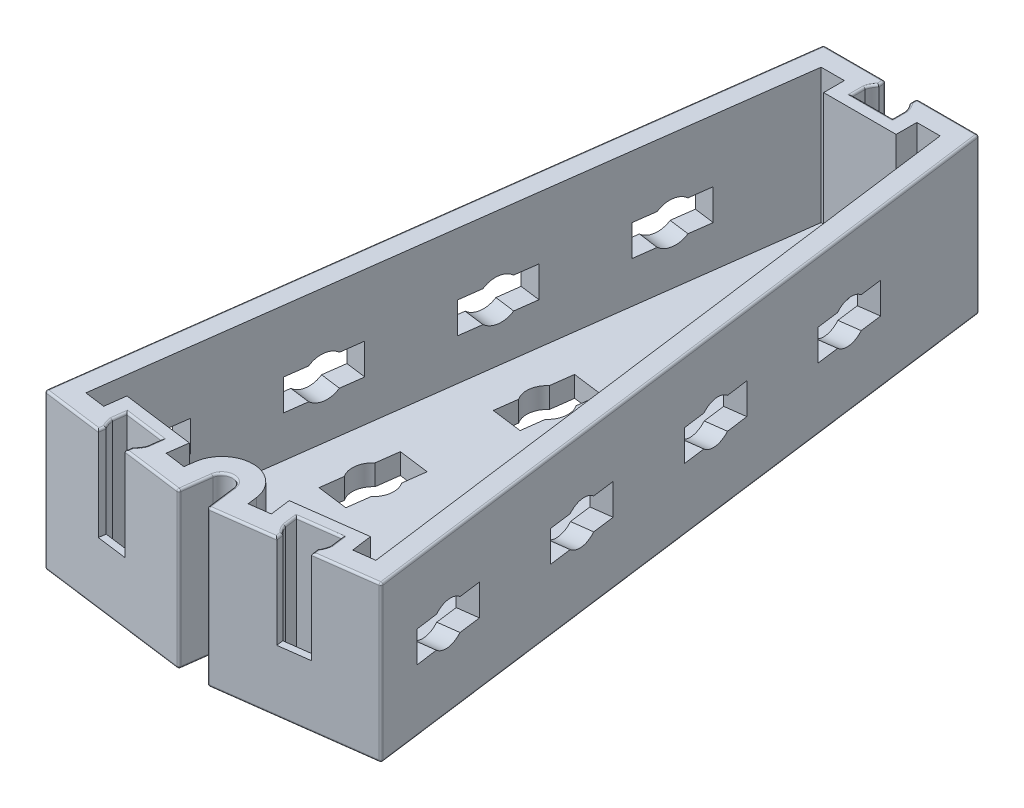
SolidWorks part; units mm, degrees
ref_plane "前视基准面" through (0, 0, 0) normal (0, 0, 1) x (1, 0, 0)
ref_plane "上视基准面" through (0, 0, 0) normal (0, 1, 0) x (1, 0, 0)
ref_plane "右视基准面" through (0, 0, 0) normal (1, 0, 0) x (0, 0, -1)
sketch "草图1" plane through (0, 0, 0) normal (0, 1, 0) x (1, 0, 0)
  line L0 (0, 0) -> (-7.5, 0)
  line L1 (0, 0) -> (7.5, 0)
  line L2 (-7.5, 0) -> (-16.25, -66.4628)
  line L3 (7.5, 0) -> (16.25, -66.4628)
  line L4 (-16.25, -66.4628) -> (-1.3783, -68.4207)
  line L5 (16.25, -66.4628) -> (1.3783, -68.4207)
  line L6 (-1.3783, -68.4207) -> (-0.9914, -65.4821)
  line L7 (1.3783, -68.4207) -> (0.9914, -65.4821)
  arc A0 (0.9914, -65.4821) -> (-0.9914, -65.4821) centre (0, -65.6126) ccw
  dimension "D11" = 2
  dimension "D1" = 7.5
  dimension "D2" = 7.5
  dimension "D3" = 97.5
  dimension "D4" = 97.5
  dimension "D5" = 32.5
  dimension "D6" = 15
  dimension "D7" = 67.0364
  dimension "D8" = 90
  dimension "D9" = 15
  dimension "D10" = 90
extrude "凸台-拉伸1" add sketch "草图1" along normal blind 15
sketch "草图2" plane through (0, 15, 0) normal (0, 1, 0) x (1, 0, 0)
  line L7 (-3.5, -2) -> (-3.5, -4)
  line L8 (-3.5, -4) -> (3.5, -4)
  line L9 (3.5, -4) -> (3.5, -2)
  line L10 (-3.5, -2) -> (-5.746, -2)
  line L11 (-12.0232, -65.0021) -> (-11.7621, -63.0192)
  line L12 (-11.7621, -63.0192) -> (-4.822, -63.9329)
  line L13 (-4.822, -63.9329) -> (-5.0831, -65.9157)
  line L14 (5.746, -2) -> (-5.746, -2)
  line L15 (-5.746, -2) -> (-14.0061, -64.741)
  line L16 (-14.0061, -64.741) -> (-3.1002, -66.1768)
  line L17 (-3.1002, -66.1768) -> (-2.9743, -65.221)
  line L18 (2.9743, -65.221) -> (3.1002, -66.1768)
  line L19 (3.1002, -66.1768) -> (14.0061, -64.741)
  line L20 (14.0061, -64.741) -> (5.746, -2)
  line L21 (5.746, -2) -> (3.5, -2)
  line L22 (-5.746, -2) -> (-14.0061, -64.741)
  line L23 (-14.0061, -64.741) -> (-12.0232, -65.0021)
  line L24 (-3.1002, -66.1768) -> (-2.9743, -65.221)
  line L25 (2.9743, -65.221) -> (3.1002, -66.1768)
  line L26 (3.1002, -66.1768) -> (5.0831, -65.9157)
  line L27 (14.0061, -64.741) -> (5.746, -2)
  line L28 (-5.0831, -65.9157) -> (-3.1002, -66.1768)
  line L29 (12.0232, -65.0021) -> (11.7621, -63.0192)
  line L30 (11.7621, -63.0192) -> (4.822, -63.9329)
  line L31 (4.822, -63.9329) -> (5.0831, -65.9157)
  line L32 (12.0232, -65.0021) -> (14.0061, -64.741)
  arc A2 (2.9743, -65.221) -> (-2.9743, -65.221) centre (0, -65.6126) ccw
  arc A3 (2.9743, -65.221) -> (-2.9743, -65.221) centre (0, -65.6126) ccw
  dimension "D2" = 3.5
  dimension "D3" = 3.5
  dimension "D4" = 2
  dimension "D5" = 90
  dimension "D6" = 2
  dimension "D7" = 2
  dimension "D8" = 2
  dimension "D9" = 90
  dimension "D10" = 2
  dimension "D11" = 2
  dimension "D12" = 2
  dimension "D1" = 2
extrude "切除-拉伸1" cut sketch "草图2" against normal blind 13
sketch "草图3" plane through (0, 15, 0) normal (0, 1, 0) x (1, 0, 0)
  line L0 (0, 0) -> (0, -2) construction
  line L1 (0, -2) -> (0, -2.8) construction
  line L2 (1.95, -2.8) -> (-1.95, -2.8)
  line L3 (-1.95, -2.8) -> (-1.95, -1.5556)
  line L4 (1.5, 0) -> (-1.5, 0)
  line L5 (-1.5, 0) -> (-1.5, -0.6771)
  line L6 (1.95, -2.8) -> (1.95, -1.5556)
  line L7 (1.5, 0) -> (1.5, -0.6771)
  arc A0 (-1.5, -0.6771) -> (-1.95, -1.5556) centre (0, -2) ccw
  arc A1 (1.5, -0.6771) -> (1.95, -1.5556) centre (0, -2) cw
  dimension "D1" = 2
  dimension "D2" = 0.8
  dimension "D3" = 1.5
  dimension "D4" = 1.95
extrude "切除-拉伸2" cut sketch "草图3" against normal up to next
sketch "草图4" plane through (0, 15, 0) normal (0, 1, 0) x (1, 0, 0)
  line L0 (-8.8142, -67.4418) -> (-8.5531, -65.4589) construction
  line L1 (-16.25, -66.4628) -> (-1.3783, -68.4207) construction
  line L2 (-8.5531, -65.4589) -> (-8.4487, -64.6657) construction
  line L3 (-7.327, -67.6376) -> (-10.3013, -67.246)
  line L4 (-10.3013, -67.246) -> (-10.2129, -66.5747)
  line L5 (-6.5154, -64.9203) -> (-10.382, -64.4112)
  line L6 (-10.382, -64.4112) -> (-10.5444, -65.645)
  line L7 (-7.327, -67.6376) -> (-7.2386, -66.9663)
  line L8 (-6.5154, -64.9203) -> (-6.6778, -66.154)
  arc A0 (-10.5444, -65.645) -> (-10.2129, -66.5747) centre (-8.5531, -65.4589) ccw
  arc A1 (-6.6778, -66.154) -> (-7.2386, -66.9663) centre (-8.5531, -65.4589) cw
  dimension "D7" = 2
  dimension "D1" = 2
  dimension "D2" = 0.8
  dimension "D4" = 1.5
  dimension "D5" = 1.95
extrude "切除-拉伸3" cut sketch "草图4" against normal blind 13.5
sketch "草图5" plane through (0, 1.5, 0) normal (0, 1, 0) x (1, 0, 0)
  line L0 (-10.2129, -66.5747) -> (-7.2386, -66.9663)
  line L6 (-7.327, -67.6376) -> (-7.2386, -66.9663)
  line L7 (-6.6778, -66.154) -> (-6.5154, -64.9203)
  line L8 (-6.5154, -64.9203) -> (-10.382, -64.4112)
  line L9 (-10.382, -64.4112) -> (-10.5444, -65.645)
  line L10 (-10.2129, -66.5747) -> (-10.3013, -67.246)
  line L11 (-10.3013, -67.246) -> (-7.327, -67.6376)
  line L12 (-7.327, -67.6376) -> (-7.2386, -66.9663)
  line L16 (-10.2129, -66.5747) -> (-10.3013, -67.246)
  line L17 (-10.3013, -67.246) -> (-7.327, -67.6376)
  arc A2 (-7.2386, -66.9663) -> (-6.6778, -66.154) centre (-8.5531, -65.4589) ccw
  arc A3 (-10.5444, -65.645) -> (-10.2129, -66.5747) centre (-8.5531, -65.4589) ccw
  dimension "D1" = 0
extrude "凸台-拉伸2" add sketch "草图5" along normal blind 4.5
mirror "镜向1" about plane through (0, 0, 0) normal (1, 0, 0) of "凸台-拉伸2", "切除-拉伸3"
sketch "草图6" plane through (0, 0, 0) normal (0, -1, 0) x (1, 0, 0)
  line L0 (0, 0) -> (0, 7.5) construction
  line L1 (0, 7.5) -> (0, 15) construction
  line L2 (0, 15) -> (0, 22.5) construction
  circle A0 centre (0, 7.5) radius 2
  circle A1 centre (0, 15) radius 2
  circle A2 centre (0, 22.5) radius 2
  dimension "D2" = 4
  dimension "D5" = 4
  dimension "D6" = 4
  dimension "D1" = 7.5
  dimension "D3" = 7.5
  dimension "D4" = 7.5
extrude "切除-拉伸4" cut sketch "草图6" against normal up to next
sketch "草图7" plane through (-7.3722, 0, -0.9706) normal (-0.9914, 0, -0.1305) x (-0.1305, 0, 0.9914)
  line L0 (68.0153, 7.5) -> (60.5153, 7.5) construction
  line L1 (68.0153, 15) -> (68.0153, 0) construction
  line L2 (64.0153, 9) -> (64.0153, 6)
  line L3 (64.0153, 9) -> (61.8382, 9)
  line L4 (64.0153, 6) -> (61.8382, 6)
  line L5 (57.0153, 9) -> (57.0153, 6)
  line L6 (64.0153, 9) -> (57.0153, 6) construction
  line L7 (64.0153, 6) -> (57.0153, 9) construction
  line L8 (59.1924, 6) -> (57.0153, 6)
  line L9 (59.1924, 9) -> (57.0153, 9)
  arc A0 (59.1924, 6) -> (61.8382, 6) centre (60.5153, 7.5) ccw
  arc A1 (61.8382, 9) -> (59.1924, 9) centre (60.5153, 7.5) ccw
  dimension "D2" = 4
  dimension "D1" = 7.5
  dimension "D3" = 7
  dimension "D4" = 3
extrude "切除-拉伸5" cut sketch "草图7" against normal up to next
pattern_linear "阵列(线性)1" count 4 spacing 15 along (0.1305, 0, -0.9914) of "切除-拉伸5"
sketch "草图8" plane through (0, 0, 0) normal (0, -1, 0) x (1, 0, 0)
  line L0 (-8.8142, 67.4418) -> (-7.8352, 60.006) construction
  line L1 (-16.25, 66.4628) -> (-1.3783, 68.4207) construction
  line L2 (-8.8655, 56.3401) -> (-5.8912, 56.7317)
  line L3 (-8.8655, 56.3401) -> (-9.1497, 58.4986)
  line L4 (-5.8912, 56.7317) -> (-6.1754, 58.8902)
  line L5 (-9.7792, 63.2802) -> (-6.8049, 63.6718)
  line L6 (-8.8655, 56.3401) -> (-6.8049, 63.6718) construction
  line L7 (-5.8912, 56.7317) -> (-9.7792, 63.2802) construction
  line L8 (-9.4951, 61.1217) -> (-9.7792, 63.2802)
  line L9 (-6.5207, 61.5133) -> (-6.8049, 63.6718)
  arc A0 (-9.4951, 61.1217) -> (-9.1497, 58.4986) centre (-7.8352, 60.006) ccw
  arc A1 (-6.1754, 58.8902) -> (-6.5207, 61.5133) centre (-7.8352, 60.006) ccw
  dimension "D3" = 4
  dimension "D1" = 7.5
  dimension "D2" = 90
  dimension "D4" = 90
  dimension "D5" = 3
  dimension "D6" = 7
extrude "切除-拉伸6" cut sketch "草图8" against normal up to next
pattern_linear "阵列(线性)2" count 3 spacing 15 along (0.1305, 0, -0.9914) of "切除-拉伸6"
mirror "镜向2" about plane through (0, 0, 0) normal (1, 0, 0) of "阵列(线性)1", "阵列(线性)2"
fillet "圆角1" radius 0.2 56 edges at (-4.3527, 15, 68.0292) (1.1849, 0, 66.9514) (0, 0, 64.6126) (-1.1849, 0, 66.9514) (13.2757, 15, 66.8544) (16.25, 7.5, 66.4628) (8.8142, 0, 67.4418) (4.3527, 15, 68.0292) (1.3783, 7.5, 68.4207) (1.1849, 15, 66.9514) (-1.1849, 15, 66.9514) (0, 15, 64.6126) (-1.3783, 7.5, 68.4207) (-13.2757, 15, 66.8544) (-8.8142, 0, 67.4418) (-16.25, 7.5, 66.4628) (-11.875, 15, 33.2314) (-11.875, 0, 33.2314) (4.5, 15, 0) (-4.5, 15, 0) (-7.5, 7.5, 0) (-4.5, 0, 0) (4.5, 0, 0) (7.5, 7.5, 0) (11.875, 0, 33.2314) (11.875, 15, 33.2314) (10.2571, 15, 66.9103) (10.4369, 15, 66.1306) (10.4632, 15, 65.0281) (8.4487, 15, 64.6657) (6.5966, 15, 65.5372) (6.9073, 15, 66.5953) (7.2828, 15, 67.3019) (-7.2828, 15, 67.3019) (-6.9073, 15, 66.5953) (-6.5966, 15, 65.5372) (-8.4487, 15, 64.6657) (-10.4632, 15, 65.0281) (-10.4369, 15, 66.1306) (-10.2571, 15, 66.9103) (1.5, 15, 0.3386) (1.78, 15, 1.0882) (1.95, 15, 2.1778) (0, 15, 2.8) (-1.95, 15, 2.1778) (-1.78, 15, 1.0882) (-1.5, 15, 0.3386) (1.5, 0, 0.3386) (1.78, 0, 1.0882) (1.95, 0, 2.1778) (0, 0, 2.8) (-1.95, 0, 2.1778) (-1.78, 0, 1.0882) (-1.5, 0, 0.3386) (1.5, 7.5, 0) (-1.5, 7.5, 0)
